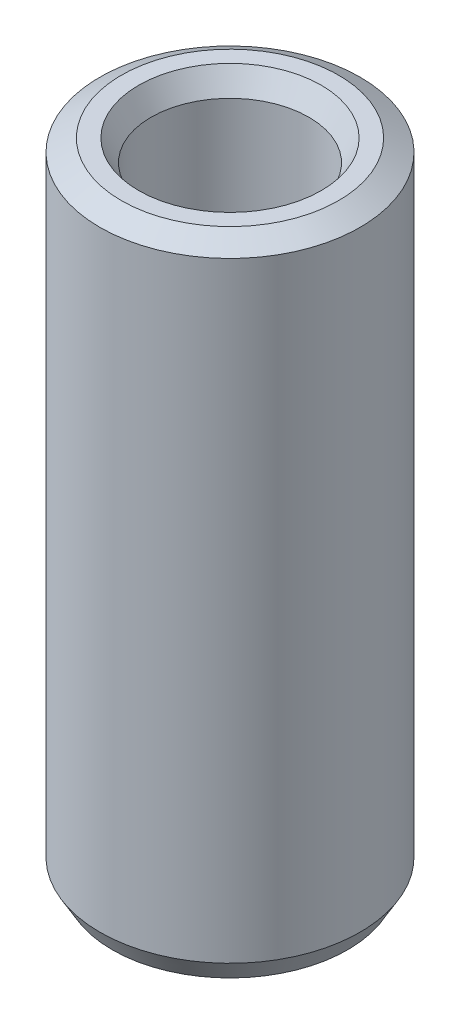
SolidWorks part; units mm, degrees
ref_plane "Front Plane" through (0, 0, 0) normal (0, 0, 1) x (1, 0, 0)
ref_plane "Top Plane" through (0, 0, 0) normal (0, 1, 0) x (1, 0, 0)
ref_plane "Right Plane" through (0, 0, 0) normal (1, 0, 0) x (0, 0, -1)
sketch "Sketch1" plane through (0, 0, 0) normal (0, 1, 0) x (1, 0, 0)
  circle A0 centre (0, 0) radius 22.5
  dimension "SLEEVE_OD" = 45
extrude "Boss-Extrude1" add sketch "Sketch1" along normal blind 111.4019
sketch "Sketch2" plane through (0, 0, 0) normal (0, 1, 0) x (1, 0, 0)
  circle A0 centre (0, 0) radius 13.6417
  dimension "BORE_D" = 27.2833
extrude "Cut-Extrude1" cut sketch "Sketch2" along normal through all
chamfer "Chamfer1" distance 2.1451 angle 60 4 edges at (0, 111.4019, 13.6417) (0, 0, 13.6417) (0, 0, 22.5) (0, 111.4019, 22.5) first distance on face at (0, 111.4019, 13.6417) first distance on face at (0, 0, 13.6417) first distance on face at (0, 111.4019, 22.5)
